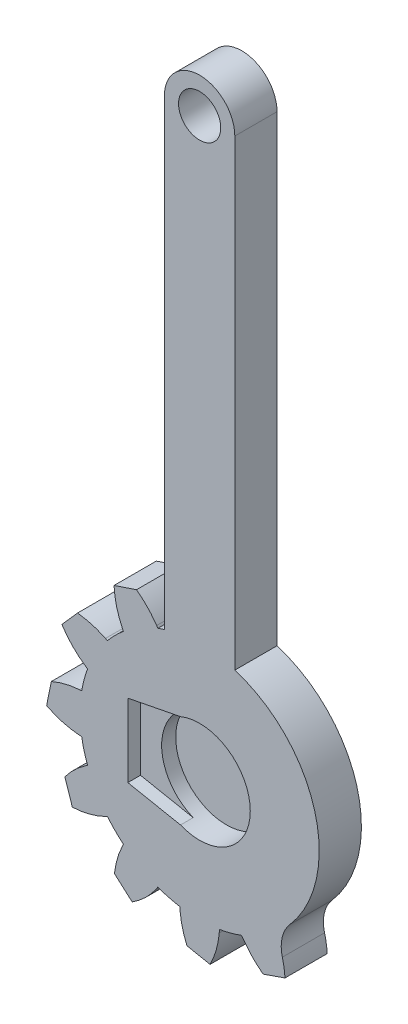
SolidWorks part; units mm, degrees
ref_plane "Front Plane" through (0, 0, 0) normal (0, 0, 1) x (1, 0, 0)
ref_plane "Top Plane" through (0, 0, 0) normal (0, 1, 0) x (1, 0, 0)
ref_plane "Right Plane" through (0, 0, 0) normal (1, 0, 0) x (0, 0, -1)
ref_plane "Plane1" through (0, 0, 1.9) normal (0, 0, 1) x (1, 0, 0)
sketch "Sketch1" plane through (0, 0, 1.9) normal (0, 0, 1) x (1, 0, 0)
  line L1 (2.5, 8.124) -> (2.5, 41)
  line L2 (-2.5, 41) -> (-2.5, 8.124)
  line L3 (-2.9677, 7.9651) -> (-3.0542, 8.0933)
  line L4 (-5.4819, 6.6916) -> (-5.4141, 6.5527)
  line L5 (-6.5527, 5.4141) -> (-6.6916, 5.4819)
  line L6 (-8.0933, 3.0542) -> (-7.9651, 2.9677)
  line L7 (-8.3818, 1.4124) -> (-8.5361, 1.4016)
  line L8 (-8.5361, -1.4016) -> (-8.3818, -1.4124)
  line L9 (-7.9651, -2.9677) -> (-8.0933, -3.0542)
  line L10 (-6.6916, -5.4819) -> (-6.5527, -5.4141)
  line L11 (-5.4141, -6.5527) -> (-5.4819, -6.6916)
  line L12 (-3.0542, -8.0933) -> (-2.9677, -7.9651)
  line L13 (-0.0002, -11.9849) -> (-0.0001, -8.5) construction
  line L14 (-1.4126, -8.3818) -> (-1.3931, -8.6097)
  line L15 (1.3928, -8.6097) -> (1.4123, -8.3819)
  line L16 (1.6803, -8.5) -> (-1.6806, -8.5) construction
  line L17 (5.9921, -10.3794) -> (4.2498, -7.3614) construction
  line L18 (2.9674, -7.9652) -> (3.3928, -8.4983)
  line L19 (5.6629, -7.1878) -> (5.4139, -6.5528)
  line L20 (13.4272, -2.0631) -> (-4.9277, -12.6596) construction
  arc A1 (2.5, 41) -> (-2.5, 41) centre (0, 41) ccw
  arc A2 (-2.5, 8.124) -> (-2.9677, 7.9651) centre (0, 0) ccw
  arc A3 (-3.0542, 8.0933) -> (-5.9946, 10.3829) centre (-8.0284, 4.7381) ccw
  arc A4 (-5.9946, 10.3829) -> (-5.4819, 6.6916) centre (-0.0891, 9.3218) ccw
  arc A5 (-5.4141, 6.5527) -> (-6.5527, 5.4141) centre (0, 0) ccw
  arc A6 (-6.6916, 5.4819) -> (-10.3829, 5.9946) centre (-9.3218, 0.0891) ccw
  arc A7 (-10.3829, 5.9946) -> (-8.0933, 3.0542) centre (-4.7381, 8.0284) ccw
  arc A8 (-7.9651, 2.9677) -> (-8.3818, 1.4124) centre (0, 0) ccw
  arc A9 (-8.5361, 1.4016) -> (-11.9891, 0) centre (-8.1175, -4.5837) ccw
  arc A10 (-11.9891, 0) -> (-8.5361, -1.4016) centre (-8.1175, 4.5837) ccw
  arc A11 (-8.3818, -1.4124) -> (-7.9651, -2.9677) centre (0, 0) ccw
  arc A12 (-8.0933, -3.0542) -> (-10.3829, -5.9946) centre (-4.7381, -8.0284) ccw
  arc A13 (-10.3829, -5.9946) -> (-6.6916, -5.4819) centre (-9.3218, -0.0891) ccw
  arc A14 (-6.5527, -5.4141) -> (-5.4141, -6.5527) centre (0, 0) ccw
  arc A15 (-5.4819, -6.6916) -> (-5.9946, -10.3829) centre (-0.0891, -9.3218) ccw
  arc A16 (-5.9946, -10.3829) -> (-3.0542, -8.0933) centre (-8.0284, -4.7381) ccw
  arc A17 (-2.9677, -7.9651) -> (-1.4126, -8.3818) centre (0, 0) ccw
  circle A18 centre (0, 41) radius 1.5
  arc A19 (-2.5, 8.124) -> (-1.4126, -8.3818) centre (0, 0) cw construction
  arc A20 (-1.3931, -8.6097) -> (-0.0002, -11.9849) centre (4.6403, -8.0947) ccw
  arc A21 (-0.0002, -11.9849) -> (1.3928, -8.6097) centre (-4.6405, -8.0946) ccw
  arc A22 (1.4123, -8.3819) -> (2.9674, -7.9652) centre (0.0042, -0.0156) ccw
  arc A23 (8.5, 0) -> (5.4139, -6.5528) centre (0, 0) cw
  arc A24 (3.3928, -8.4983) -> (5.9921, -10.3794) centre (8.0792, -4.7591) ccw
  arc A25 (5.9921, -10.3794) -> (5.6629, -7.1878) centre (0.0812, -9.3763) ccw
  arc A26 (8.5, 0) -> (2.5, 8.124) centre (0, 0) ccw
  dimension "D2" = 0.0891
  dimension "D3" = 8.5
  dimension "D4" = 6
  dimension "D13" = 3
  dimension "D14" = 1.61
  dimension "D17" = 2.8249
  dimension "D18" = 3.87
  dimension "D19" = 0.682
  dimension "D22" = 1.61
  dimension "D5" = 2.9677
  dimension "D6" = 3.0542
  dimension "D7" = 4.7381
  dimension "D8" = 5.4141
  dimension "D9" = 5.4819
  dimension "D10" = 6.5527
  dimension "D11" = 8.1175
  dimension "D12" = 8.3818
  dimension "D15" = 41
  dimension "D16" = 5
  dimension "D20" = 3.87
  dimension "D21" = 2.8249
extrude "Boss-Extrude1" add sketch "Sketch1" against normal blind 3
ref_plane "Plane2" through (0, 0, 1.9) normal (0, 0, -1) x (-1, 0, 0)
sketch "Sketch4" plane through (0, 0, 1.9) normal (0, 0, 1) x (1, 0, 0)
  line L0 (-5.1029, -2.6) -> (-1.3588, -3.3337)
  line L1 (-1.3588, 3.3337) -> (-5.1029, 2.6)
  line L2 (-5.1029, 2.6) -> (-5.1029, -2.6)
  arc A0 (-1.3588, -3.3337) -> (-1.3588, 3.3337) centre (0, 0) cw
extrude "Cut-Extrude2" cut sketch "Sketch4" against normal blind 0.9
sketch "Sketch5" plane through (0, 0, 0) normal (0, 1, 0) x (1, 0, 0)
  line L0 (3.6, 0) -> (0, 0)
  line L1 (0, 0) -> (0, -3)
  line L2 (0, -3) -> (3.6, -3)
  line L3 (3.6, -3) -> (3.6, 0)
  line L4 (0, 0) -> (0, -3) construction
revolve "Cut-Revolve1" cut sketch "Sketch5" angle 360 about L4 reverse direction yes
chamfer "Chamfer1" distance 1.4124 angle 61.288 7 edges at (-10.3829, -5.9946, 0.4) (-5.9946, -10.3829, 0.4) (-11.9891, 0, 0.4) (-10.3829, 5.9946, 0.4) (-5.9946, 10.3829, 0.4) (5.9921, -10.3794, 0.4) (-0.0002, -11.9849, 0.4) first distance on face at (-8.5169, -5.8852, 0.4) first distance on face at (-4.4332, -9.3551, 0.4) first distance on face at (-10.3184, -0.8383, 0.4) first distance on face at (-9.3551, 4.4332, 0.4) first distance on face at (-5.8852, 8.5169, 0.4) first distance on face at (5.9362, -8.7724, 0.4) first distance on face at (0.8265, -10.3511, 0.4)
fillet "Fillet1" radius 2.5 1 edges at (5.4139, -6.5528, 0.4) tangent propagation no
